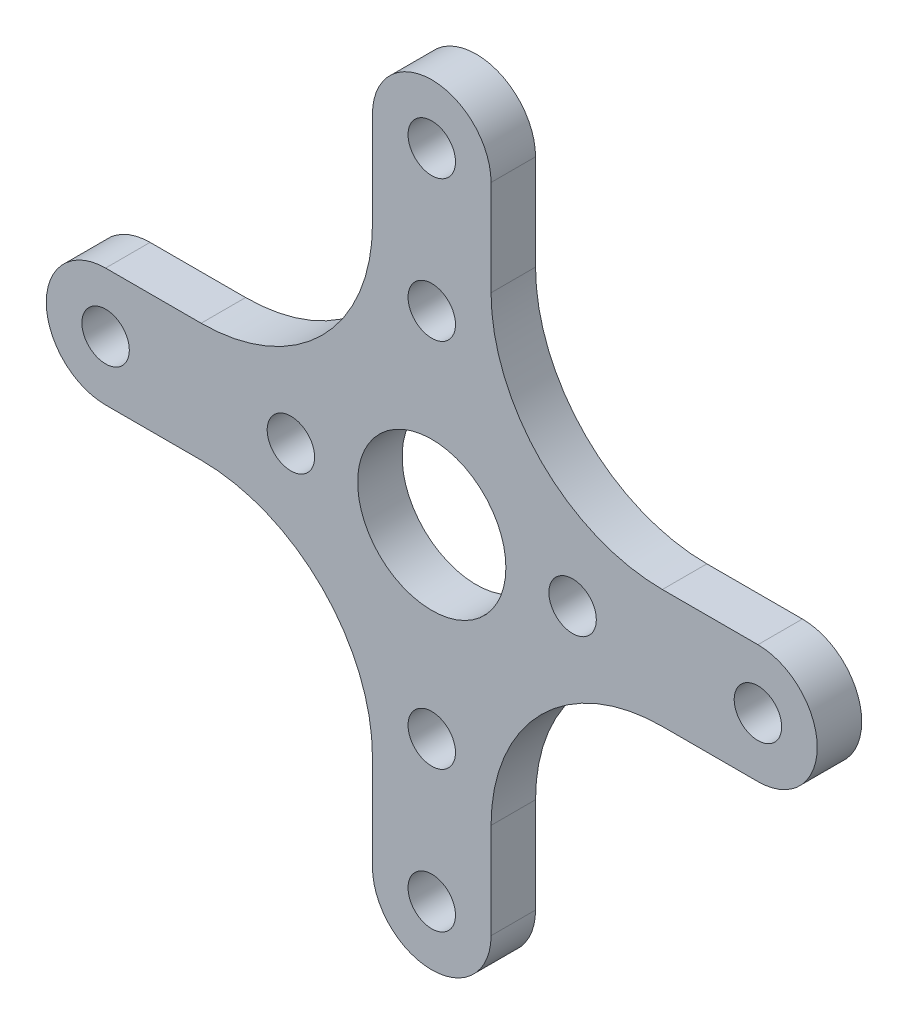
SolidWorks part; units mm, degrees
ref_plane "Front Plane" through (0, 0, 0) normal (0, 0, 1) x (1, 0, 0)
ref_plane "Top Plane" through (0, 0, 0) normal (0, 1, 0) x (1, 0, 0)
ref_plane "Right Plane" through (0, 0, 0) normal (1, 0, 0) x (0, 0, -1)
sketch "Эскиз1" plane through (0, 0, 0) normal (0, 0, 1) x (1, 0, 0)
  line L0 (0, 96.3109) -> (0, -96.3109) construction
  line L1 (-81.2237, 0) -> (103.8753, 0) construction
  line L2 (-22, 4) -> (-15.5563, 4)
  line L3 (-4, 15.5563) -> (-4, 22)
  line L4 (22, 4) -> (15.5563, 4)
  line L5 (4, 15.5563) -> (4, 22)
  line L6 (22, -4) -> (15.5563, -4)
  line L7 (4, -15.5563) -> (4, -22)
  line L8 (-4, -15.5563) -> (-4, -22)
  line L9 (-22, -4) -> (-15.5563, -4)
  circle A0 centre (0, 0) radius 22 construction
  circle A1 centre (0, 22) radius 1.6
  circle A2 centre (22, 0) radius 1.6
  circle A3 centre (0, -22) radius 1.6
  circle A4 centre (-22, 0) radius 1.6
  circle A5 centre (0, 0) radius 5
  circle A6 centre (-9.5, 0) radius 1.6
  circle A7 centre (9.5, 0) radius 1.6
  circle A8 centre (0, 12.5) radius 1.6
  circle A9 centre (0, -12.5) radius 1.6
  arc A10 (-15.5563, 4) -> (-4, 15.5563) centre (-15.5563, 15.5563) ccw
  arc A11 (-4, 22) -> (4, 22) centre (0, 22) cw
  arc A12 (-22, 4) -> (-22, -4) centre (-22, 0) ccw
  arc A13 (22, 4) -> (22, -4) centre (22, 0) cw
  arc A14 (15.5563, 4) -> (4, 15.5563) centre (15.5563, 15.5563) cw
  arc A15 (15.5563, -4) -> (4, -15.5563) centre (15.5563, -15.5563) ccw
  arc A16 (-4, -22) -> (4, -22) centre (0, -22) ccw
  arc A17 (-15.5563, -4) -> (-4, -15.5563) centre (-15.5563, -15.5563) cw
  point P13 (0, 0)
  point P32 (0, 0)
  point P33 (-15.5563, 15.5563)
  dimension "D1" = 44
  dimension "D2" = 3.2
  dimension "D4" = 3.2
  dimension "D6" = 3.2
  dimension "D9" = 10
  dimension "D3" = 19
  dimension "D5" = 9.5
  dimension "D7" = 25
  dimension "D8" = 12.5
extrude "Бобышка-Вытянуть1" add sketch "Эскиз1" along normal mid plane 3
equation "\"D5@Эскиз1\"=\"D3@Эскиз1\"/2"
equation "\"D8@Эскиз1\"=\"D7@Эскиз1\"/2"
